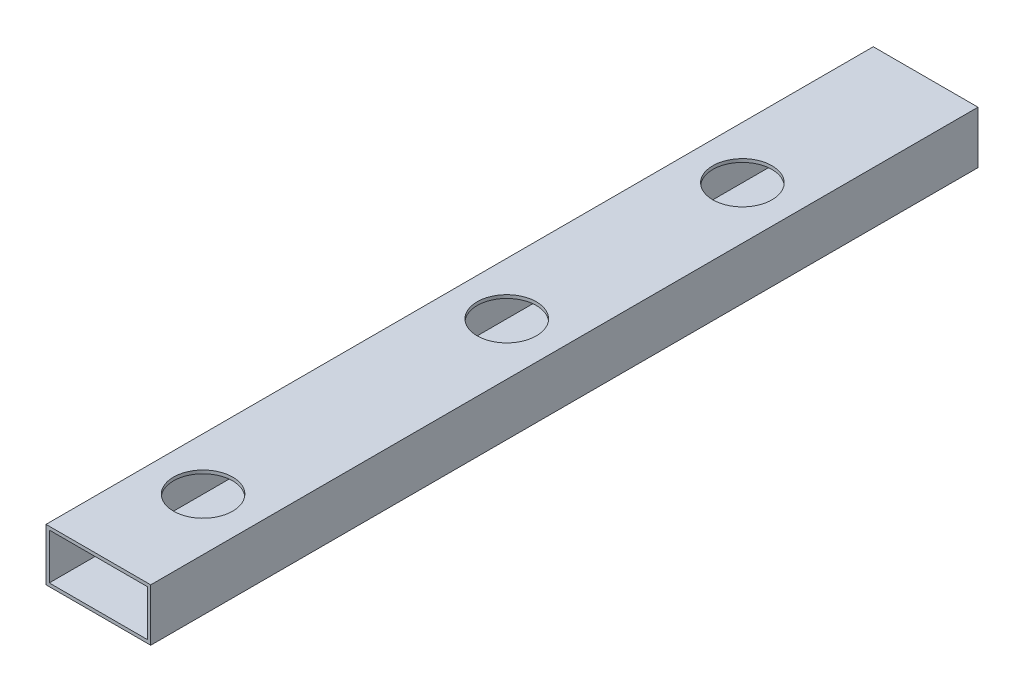
SolidWorks part; units mm, degrees
ref_plane "Front Plane" through (0, 0, 0) normal (0, 0, 1) x (1, 0, 0)
ref_plane "Top Plane" through (0, 0, 0) normal (0, 1, 0) x (1, 0, 0)
ref_plane "Right Plane" through (0, 0, 0) normal (1, 0, 0) x (0, 0, -1)
sketch "Sketch1" plane through (0, 0, 0) normal (0, 0, 1) x (1, 0, 0)
  line L0 (1.5875, 1.5875) -> (1.5875, 23.8125)
  line L1 (0, 0) -> (50.8, 0)
  line L2 (0, 0) -> (0, 25.4)
  line L3 (0, 25.4) -> (50.8, 25.4)
  line L4 (50.8, 0) -> (50.8, 25.4)
  line L5 (1.5875, 23.8125) -> (49.2125, 23.8125)
  line L6 (49.2125, 1.5875) -> (49.2125, 23.8125)
  line L7 (1.5875, 1.5875) -> (49.2125, 1.5875)
  dimension "D1" = 25.4
  dimension "D2" = 50.8
  dimension "D3" = 1.5875
extrude "Boss-Extrude1" add sketch "Sketch1" along normal blind 401.32
sketch "Sketch2" plane through (0, 25.4, 0) normal (0, 1, 0) x (1, 0, 0)
  line L0 (50.8, 0) -> (0, 0) construction
  line L2 (50.8, -401.32) -> (50.8, 0) construction
  circle A0 centre (25.4, -88.9) radius 14.351
  circle A1 centre (25.4, -203.2) radius 14.351
  dimension "D1" = 28.702
  dimension "D2" = 28.702
  dimension "D3" = 88.9
  dimension "D4" = 114.3
  dimension "D5" = 25.4
  dimension "D6" = 25.4
extrude "Cut-Extrude1" cut sketch "Sketch2" against normal through all
sketch "Sketch3" plane through (0, 25.4, 0) normal (0, 1, 0) x (1, 0, 0)
  line L0 (50.8, -401.32) -> (50.8, 0) construction
  line L1 (50.8, -401.32) -> (0, -401.32) construction
  circle A0 centre (25.4, -350.52) radius 14.351
  dimension "D1" = 28.702
  dimension "D2" = 25.4
  dimension "D3" = 50.8
extrude "Cut-Extrude2" cut sketch "Sketch3" against normal through all
